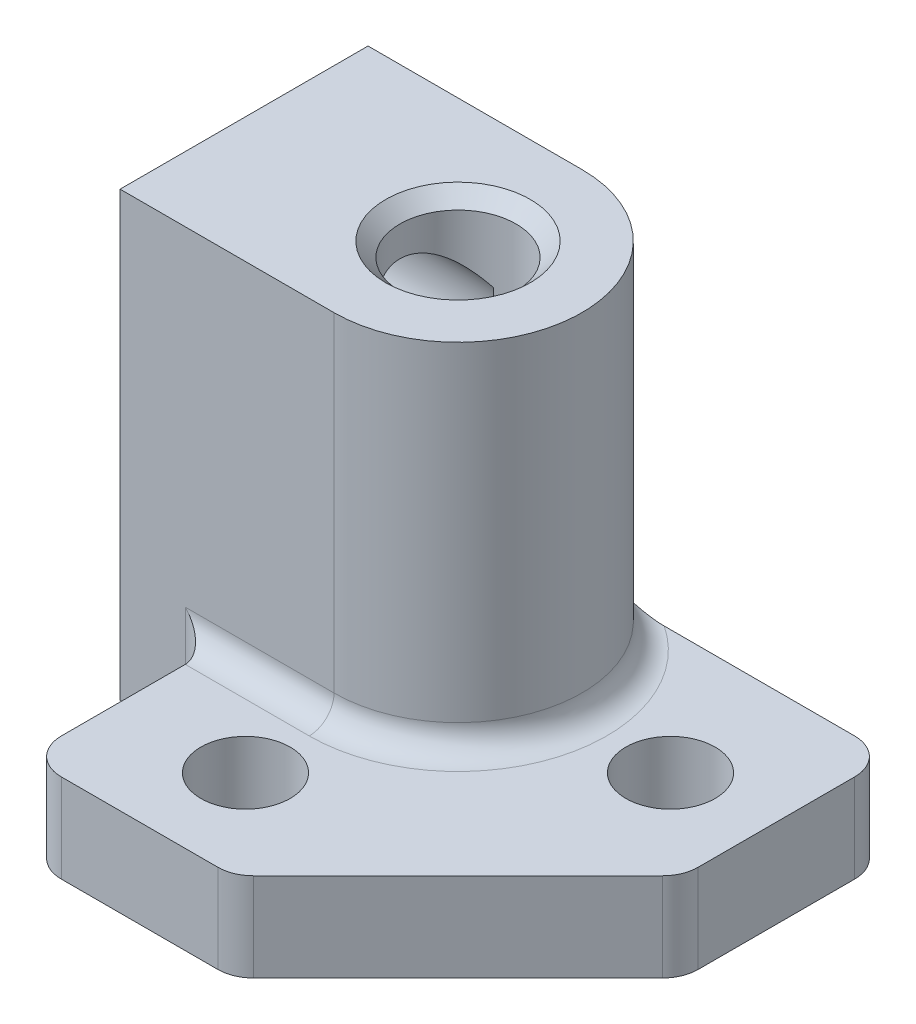
SolidWorks part; units mm, degrees
material "PLA2"
ref_plane "Front Plane" through (0, 0, 0) normal (0, 0, 1) x (1, 0, 0)
ref_plane "Top Plane" through (0, 0, 0) normal (0, 1, 0) x (1, 0, 0)
ref_plane "Right Plane" through (0, 0, 0) normal (1, 0, 0) x (0, 0, -1)
sketch "Sketch1" plane through (0, 0, 0) normal (0, 1, 0) x (1, 0, 0)
  circle A0 centre (0, 0) radius 2.0828
  circle A1 centre (0, 0) radius 4.445
  dimension "D1" = 4.1656
  dimension "D2" = 8.89
extrude "Boss-Extrude1" add sketch "Sketch1" along normal blind 12.7
sketch "Sketch2" plane through (0, 0, 0) normal (0, -1, 0) x (1, 0, 0)
  line L0 (-4.445, 0) -> (-4.445, 11.049)
  line L1 (-4.445, 11.049) -> (2.9668, 11.049)
  line L8 (2.9668, 11.049) -> (11.049, 2.9668)
  line L9 (11.049, 2.9668) -> (11.049, -4.445)
  line L10 (0, 0) -> (0, 7.62) construction
  line L11 (11.049, -4.445) -> (0, -4.445)
  line L12 (0, 0) -> (7.62, 0) construction
  circle A5 centre (0, 0) radius 4.445 construction
  arc A6 (-4.445, 0) -> (0, -4.445) centre (0, 0) ccw
  circle A7 centre (0, 7.62) radius 1.6002
  circle A8 centre (7.62, 0) radius 1.6002
  point P12 (0, 12.065)
  dimension "D1" = 3.2004
  dimension "D2" = 7.62
  dimension "D3" = 7.62
  dimension "D4" = 11.049
  dimension "D5" = 11.049
  dimension "D6" = 11.43
extrude "Boss-Extrude2" add sketch "Sketch2" along normal blind 3.175
sketch "Sketch4" plane through (0, 12.7, 0) normal (0, 1, 0) x (1, 0, 0)
  line L0 (0, 4.445) -> (-7.6708, 4.445)
  line L1 (-7.6708, 4.445) -> (-7.6708, -4.445)
  line L2 (-7.6708, -4.445) -> (0, -4.445)
  line L3 (-7.6708, 0) -> (-2.0828, 0) construction
  circle A1 centre (0, 0) radius 4.445 construction
  circle A2 centre (0, 0) radius 2.0828 construction
  circle A3 centre (0, 0) radius 2.0828 construction
  arc A4 (0, 4.445) -> (0, -4.445) centre (0, 0) ccw
  dimension "D1" = 5.588
fillet "Fillet5" radius 1.27 4 edges at (-4.445, -1.5875, 11.049) (2.9668, -1.5875, 11.049) (11.049, -1.5875, 2.9668) (11.049, -1.5875, -4.445)
extrude "Boss-Extrude3" add sketch "Sketch4" against normal up to surface (15.875 mm away) up to face at (0, -3.175, 6.0198)
chamfer "Chamfer1" distance 0.508 angle 45 1 edges at (0, 12.7, 2.0828)
sketch "Sketch3" plane through (-7.6708, 0, 0) normal (1, 0, 0) x (0, 0, -1)
  line L0 (0, 0) -> (0, 12.7) construction
  line L1 (2.0828, 12.7) -> (-2.0828, 12.7) construction
  line L2 (4.445, 12.7) -> (-4.445, 12.7) construction
  circle A0 centre (0, 8.89) radius 2.2225
  circle A1 centre (0, 2.54) radius 2.2225
  dimension "D1" = 4.445
  dimension "0.2" = 6.35
  dimension "D3" = 3.81
extrude "Cut-Extrude1" cut sketch "Sketch3" along normal blind 6.985
fillet "Fillet6" radius 0.889 3 edges at (-2.2225, 0, 4.445) (4.445, 0, 0) (-4.445, -1.5875, 4.445)
